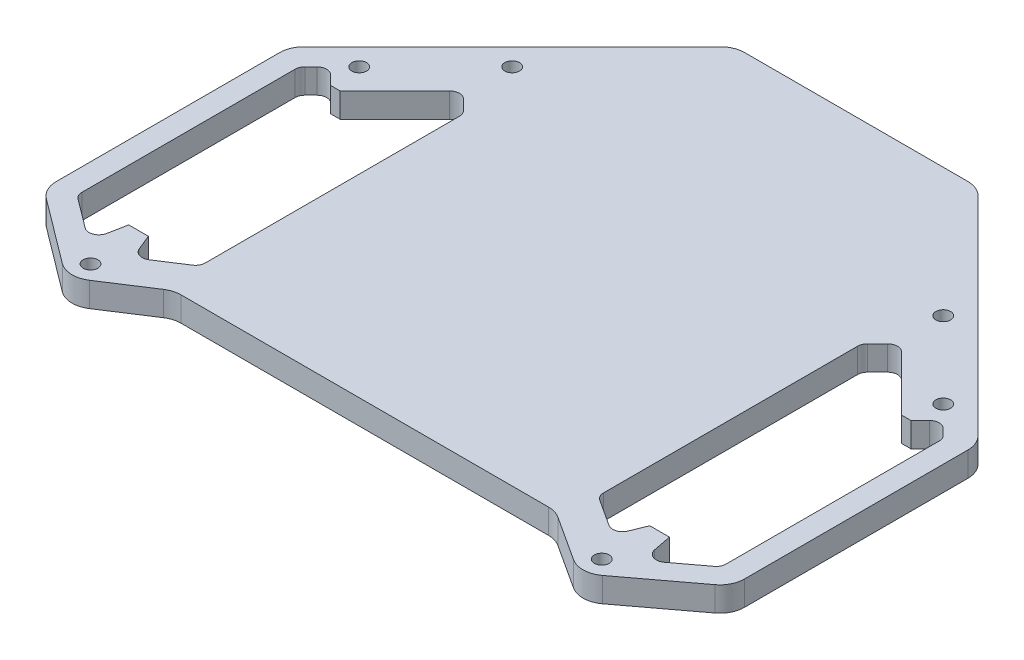
SolidWorks part; units mm, degrees
ref_plane "Front Plane" through (0, 0, 0) normal (0, 0, 1) x (1, 0, 0)
ref_plane "Top Plane" through (0, 0, 0) normal (0, 1, 0) x (1, 0, 0)
ref_plane "Right Plane" through (0, 0, 0) normal (1, 0, 0) x (0, 0, -1)
sketch "Sketch1" plane through (0, 0, 0) normal (0, 1, 0) x (1, 0, 0)
  line L0 (-52.1641, -38.6452) -> (-70, -25.2479)
  line L1 (-70, -25.2479) -> (-70, 24.7523)
  line L2 (-70, 24.7523) -> (-24.7523, 70)
  line L3 (-52.1641, -38.6452) -> (-38.8516, -30)
  line L4 (0, -30) -> (0, 70)
  line L5 (0, -30) -> (-38.8516, -30)
  line L6 (-59.397, 28.2843) -> (-43.8406, 43.8406) construction
  line L7 (-51.9976, -33.7676) -> (-63.9796, -15.3169) construction
  line L8 (-24.7523, 70) -> (0, 70)
  line L9 (0, 0) -> (-85, 0) construction
  line L10 (-43.8406, 43.8406) -> (0, 0) construction
  line L11 (-51.9976, -33.7676) -> (0, 0) construction
  line L12 (-59.0038, 22.1) -> (-57.096, 22.1)
  line L13 (-65.5, 22.1812) -> (-65.5, -23)
  line L14 (-55, -23) -> (-51, -23)
  line L15 (-40.5, 30.6005) -> (-40.5, -23)
  line L16 (-53, 22.1) -> (-53, -23) construction
  line L17 (-65.5, 22.1812) -> (-62.2925, 25.3887)
  line L18 (-62.2925, 25.3887) -> (-59.0038, 22.1)
  line L19 (-57.096, 22.1) -> (-44.5477, 34.6482)
  line L20 (-44.5477, 34.6482) -> (-40.5, 30.6005)
  line L21 (-65.5, -23) -> (-56.3366, -29.883)
  line L22 (-56.3366, -29.883) -> (-55, -23)
  line L23 (-51, -23) -> (-48.7962, -28.3876)
  line L24 (-48.7962, -28.3876) -> (-40.5, -23)
  circle A0 centre (0, 0) radius 85 construction
  circle A1 centre (-43.8406, 43.8406) radius 1.5
  circle A2 centre (-51.9976, -33.7676) radius 1.5
  circle A3 centre (-59.397, 28.2843) radius 1.5
  circle A4 centre (-63.9796, -15.3169) radius 1.5 construction
  dimension "D7" = 3
  dimension "D17" = 170
  dimension "D20" = 12.5
  dimension "D2" = 30
  dimension "D3" = 4
  dimension "D4" = 4
  dimension "D5" = 4.5
  dimension "D6" = 70
  dimension "D8" = 62
  dimension "D9" = 22
  dimension "D10" = 22
  dimension "D11" = 25
  dimension "D12" = 45.1
  dimension "D13" = 53
  dimension "D14" = 45
  dimension "D15" = 33
  dimension "D16" = 23
  dimension "D18" = 5
  dimension "D19" = 70
  dimension "D21" = 5
  dimension "D22" = 5
  dimension "D23" = 4
  dimension "D24" = 6
  dimension "D25" = 15
extrude "Boss-Extrude1" add sketch "Sketch1" along normal blind 5
fillet "Fillet1" radius 2 8 edges at (-40.5, 2.5, 23) (-48.7962, 2.5, 28.3876) (-56.3366, 2.5, 29.883) (-65.5, 2.5, 23) (-65.5, 2.5, -22.1812) (-62.2925, 2.5, -25.3887) (-40.5, 2.5, -30.6005) (-44.5477, 2.5, -34.6482)
mirror "Mirror1" about plane through (0, 5, 30) normal (-1, 0, 0) of "Fillet1", "Boss-Extrude1"
sketch "Sketch2" plane through (0, 0, 0) normal (0, 1, 0) x (1, 0, 0)
  line L0 (24.7523, 70) -> (-24.7523, 70) construction
  line L1 (-35, 70) -> (35, 70)
  line L2 (-35, 70) -> (-35, -27)
  line L3 (-35, -27) -> (35, -27)
  line L4 (35, 70) -> (35, -27)
  line L5 (-38.8516, -30) -> (38.8516, -30) construction
  dimension "D1" = 3
  dimension "D2" = 70
  dimension "D3" = 35
extrude "Cut-Extrude1" cut sketch "Sketch2" along normal blind 2.5
fillet "Fillet2" radius 5 10 edges at (-70, 2.5, 25.2479) (-70, 2.5, -24.7523) (-24.7523, 3.75, -70) (24.7523, 3.75, -70) (70, 2.5, -24.7523) (70, 2.5, 25.2479) (38.8516, 2.5, 30) (52.1641, 2.5, 38.6452) (-38.8516, 2.5, 30) (-52.1641, 2.5, 38.6452)
